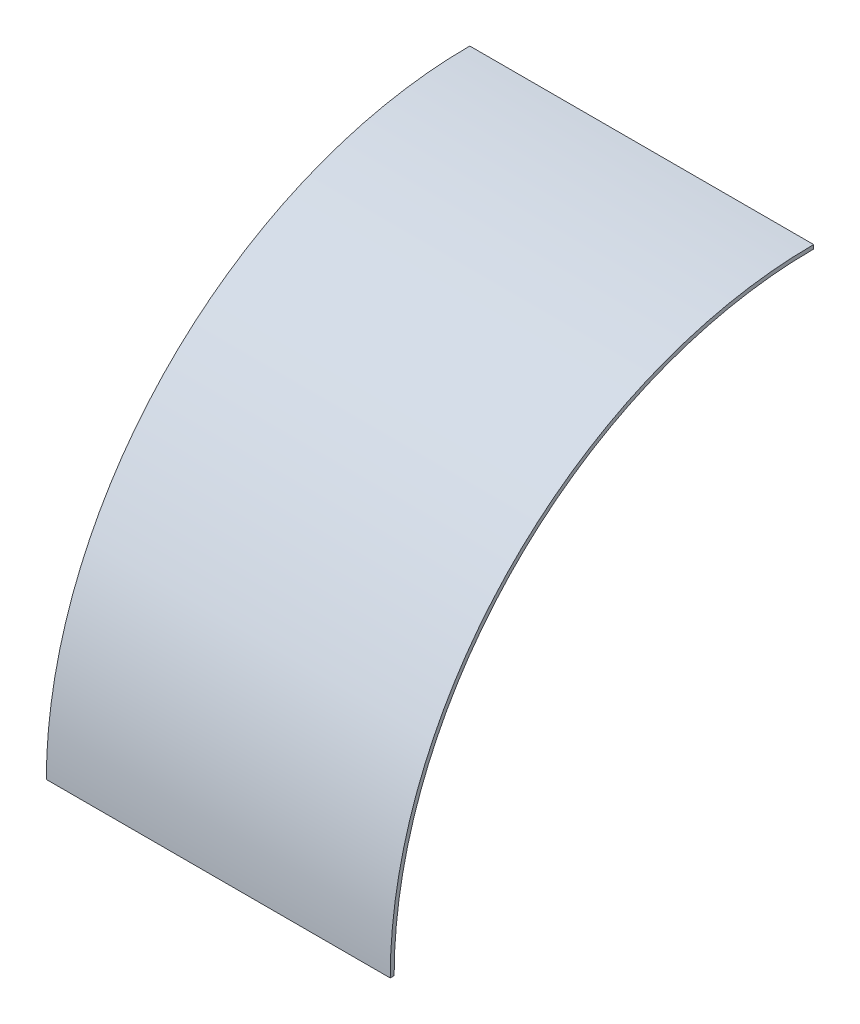
SolidWorks part; units mm, degrees
ref_plane "Front Plane" through (0, 0, 0) normal (0, 0, 1) x (1, 0, 0)
ref_plane "Top Plane" through (0, 0, 0) normal (0, 1, 0) x (1, 0, 0)
ref_plane "Right Plane" through (0, 0, 0) normal (1, 0, 0) x (0, 0, -1)
sketch "Sketch1" plane through (0, 0, 0) normal (1, 0, 0) x (0, 0, -1)
  arc A0 (0, 170.434) -> (-170.434, 0) centre (0, 0) ccw
  dimension "D1" = 340.868
extrude "Extrude-Thin1" add sketch "Sketch1" along normal blind 139.7 thin thin type one direction wall 1.5875
